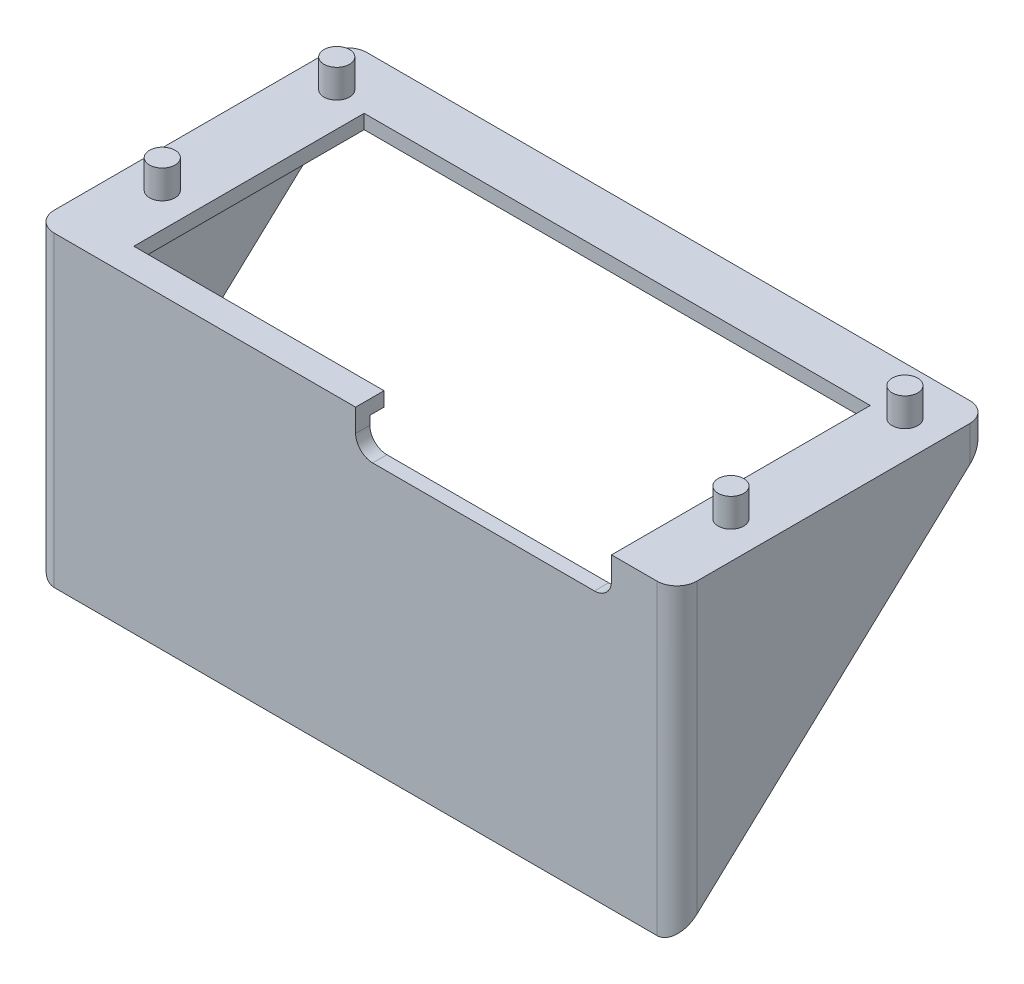
SolidWorks part; units mm, degrees
ref_plane "Front Plane" through (0, 0, 0) normal (0, 0, 1) x (1, 0, 0)
ref_plane "Top Plane" through (0, 0, 0) normal (0, 1, 0) x (1, 0, 0)
ref_plane "Right Plane" through (0, 0, 0) normal (1, 0, 0) x (0, 0, -1)
sketch "Sketch1" plane through (0, 0, 0) normal (0, 1, 0) x (1, 0, 0)
  line L1 (-52.5387, 40.0295) -> (60.4613, 40.0295)
  line L2 (-52.5387, 40.0295) -> (-52.5387, -14.9705)
  line L3 (-52.5387, -14.9705) -> (60.4613, -14.9705)
  line L4 (60.4613, 40.0295) -> (60.4613, -14.9705)
  dimension "D1" = 113
  dimension "D2" = 55
extrude "Boss-Extrude1" add sketch "Sketch1" along normal blind 3
sketch "Sketch3" plane through (60.4613, 0, 0) normal (1, 0, 0) x (0, 0, -1)
  line L0 (-14.9705, 0) -> (-14.9705, -50.9902)
  line L1 (-14.9705, -50.9902) -> (40.0295, 0)
  line L2 (40.0295, 0) -> (-14.9705, 0)
  dimension "D1" = 75
  dimension "D2" = 90
extrude "Boss-Extrude3" add sketch "Sketch3" against normal up to surface (113 mm away) up to face at (-52.5387, 1.5, -12.5295)
sketch "Sketch2" plane through (0, 3, 0) normal (0, 1, 0) x (1, 0, 0)
  line L0 (60.4613, -14.9705) -> (60.4613, 40.0295) construction
  line L1 (-52.5387, -14.9705) -> (60.4613, -14.9705) construction
  circle A0 centre (-46.0387, 31.7095) radius 2.25
  circle A1 centre (53.9613, 31.6295) radius 2.25
  circle A2 centre (53.9613, 1.0295) radius 2.25
  circle A3 centre (-46.0387, 1.0295) radius 2.25
  dimension "D1" = 4.5
  dimension "D2" = 4.5
  dimension "D3" = 4.5
  dimension "D4" = 4.5
  dimension "D5" = 100
  dimension "D6" = 100
  dimension "D7" = 6.5
  dimension "D8" = 6.5
  dimension "D9" = 30.68
  dimension "D10" = 30.6
  dimension "D11" = 16
  dimension "D12" = 16
extrude "Boss-Extrude2" add sketch "Sketch2" along normal blind 5
shell "Shell1" thickness 2.5 removed face at (3.9613, -25.4951, -12.5295)
sketch "Sketch4" plane through (0, 0.5, 0) normal (0, -1, 0) x (1, 0, 0)
  line L0 (-50.0387, -37.5295) -> (-50.0387, 12.4705) construction
  line L1 (-40.0387, 9.9705) -> (47.9613, 9.9705)
  line L2 (-40.0387, 9.9705) -> (-40.0387, -30.5295)
  line L3 (-40.0387, -30.5295) -> (47.9613, -30.5295)
  line L4 (47.9613, 9.9705) -> (47.9613, -30.5295)
  line L5 (57.9613, 12.4705) -> (57.9613, -37.5295) construction
  line L6 (57.9613, -37.5295) -> (-50.0387, -37.5295) construction
  line L7 (-50.0387, 12.4705) -> (57.9613, 12.4705) construction
  dimension "D1" = 10
  dimension "D2" = 10
  dimension "D3" = 7
  dimension "D4" = 2.5
extrude "Cut-Extrude1" cut sketch "Sketch4" against normal blind 10
fillet "Fillet2" radius 3.5 4 edges at (-52.5387, 1.5, -40.0295) (60.4613, 1.5, -40.0295) (60.4613, -23.9951, 14.9705) (-52.5387, -23.9951, 14.9705)
sketch "Sketch5" plane through (0, 0, 14.9705) normal (0, 0, 1) x (1, 0, 0)
  line L0 (-49.0387, 3) -> (56.9613, 3) construction
  line L1 (3.9613, 3) -> (48.9613, 3)
  line L2 (3.9613, 3) -> (3.9613, -4)
  line L3 (3.9613, -4) -> (48.9613, -4)
  line L4 (48.9613, 3) -> (48.9613, -4)
  line L5 (60.4613, 3) -> (60.4613, -47.7454) construction
  dimension "D1" = 11.5
  dimension "D2" = 45
  dimension "D3" = 7
extrude "Cut-Extrude2" cut sketch "Sketch5" against normal up to surface (45.5 mm away) up to face at (3.9613, 1.75, -30.5295)
fillet "Fillet3" radius 3 2 edges at (48.9613, -4, 13.7205) (3.9613, -4, 13.7205)
